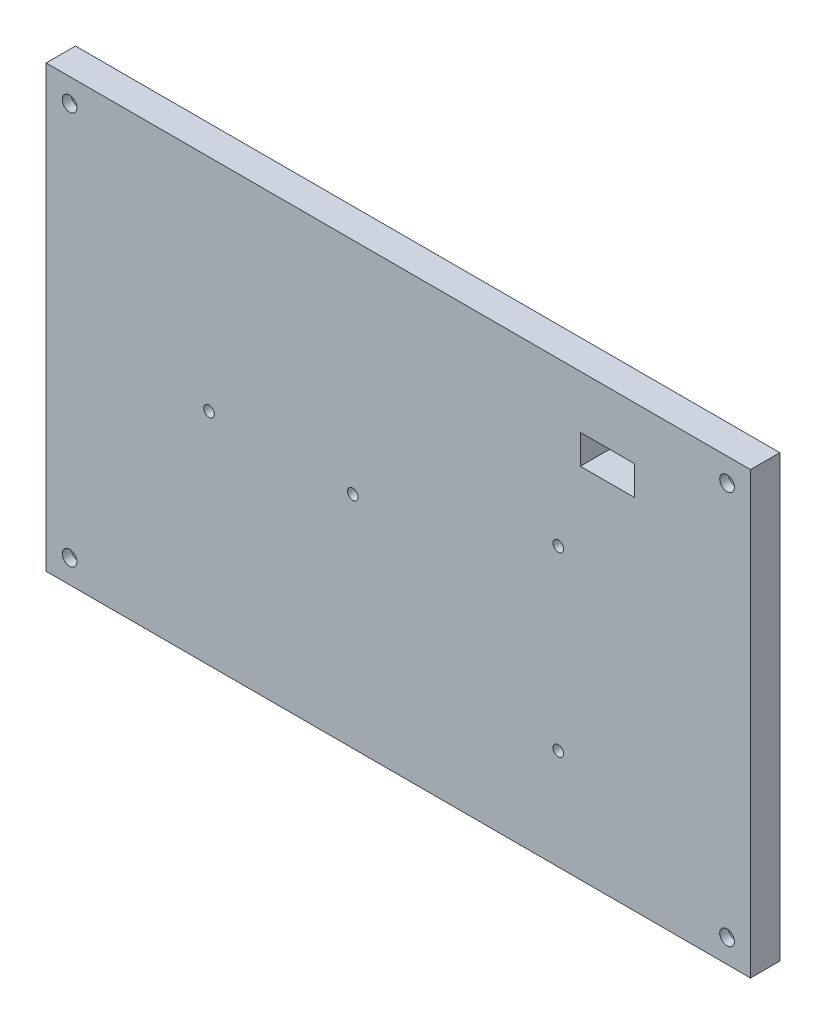
SolidWorks part; units mm, degrees
ref_plane "前视基准面" through (0, 0, 0) normal (0, 0, 1) x (1, 0, 0)
ref_plane "上视基准面" through (0, 0, 0) normal (0, 1, 0) x (1, 0, 0)
ref_plane "右视基准面" through (0, 0, 0) normal (1, 0, 0) x (0, 0, -1)
other "Configuration Table"
sketch "草图1" plane through (0, 0, 0) normal (0, 0, 1) x (1, 0, 0)
  line L9 (-120, 37.5) -> (0, 37.5)
  line L10 (-120, 37.5) -> (-120, -37.5)
  line L16 (-120, -37.5) -> (0, -37.5)
  line L17 (0, 37.5) -> (0, -37.5)
  dimension "D2" = 120
  dimension "D1" = 75
extrude "凸台-拉伸1" add sketch "草图1" along normal blind 5 contours L16 L17 L9 L10
sketch "草图2" plane through (0, 0, 0) normal (0, 0, -1) x (-1, 0, 0)
  line L0 (120, 37.5) -> (0, 37.5) construction
  line L1 (0, 37.5) -> (0, -37.5) construction
  line L2 (120, 37.5) -> (120, -37.5) construction
  line L3 (120, -37.5) -> (0, -37.5) construction
  circle A0 centre (4, 33.5) radius 2
  circle A1 centre (116, 33.5) radius 2
  circle A2 centre (4, -33.5) radius 2
  circle A3 centre (116, -33.5) radius 2
  circle A4 centre (4, 33.5) radius 1.25
  circle A5 centre (4, -33.5) radius 1.25
  circle A6 centre (116, -33.5) radius 1.25
  circle A7 centre (116, 33.5) radius 1.25
  dimension "D1" = 2.5
  dimension "D2" = 4
  dimension "D3" = 4
  dimension "D4" = 4
  dimension "D5" = 4
  dimension "D6" = 4
extrude "切除-拉伸1" cut sketch "草图2" against normal through all contours A5 | A6 | A7 | A4
extrude "切除-拉伸2" cut sketch "草图2<3>" against normal blind 3.5 contours A0 | A1 | A3 | A2
sketch "草图2<3>" plane through (0, 0, 0) normal (0, 0, -1) x (-1, 0, 0) same geometry as "草图2"
sketch "草图3" plane through (0, 0, 0) normal (0, 0, -1) x (-1, 0, 0)
  line L0 (0, 37.5) -> (0, -37.5) construction
  line L1 (19.8, 28.5) -> (29, 28.5)
  line L2 (19.8, 28.5) -> (19.8, 23.5)
  line L3 (19.8, 23.5) -> (29, 23.5)
  line L4 (29, 28.5) -> (29, 23.5)
  line L6 (120, 37.5) -> (0, 37.5) construction
  dimension "D1" = 19.8
  dimension "D2" = 9
  dimension "D3" = 5
  dimension "D4" = 9.2
extrude "切除-拉伸3" cut sketch "草图3" against normal through all
sketch "草图4" plane through (0, 0, 5) normal (0, 0, 1) x (1, 0, 0)
  circle A0 centre (-92.25, 0) radius 0.9
  circle A1 centre (-67.75, 0) radius 0.9
  dimension "D1" = 1.8
extrude "切除-拉伸4" cut sketch "草图4" against normal through all
sketch "草图5" plane through (0, 0, 5) normal (0, 0, 1) x (1, 0, 0)
  circle A0 centre (-32.75, 9.85) radius 0.9
  circle A1 centre (-32.75, -20.35) radius 0.9
  dimension "D1" = 1.8
extrude "切除-拉伸5" cut sketch "草图5" against normal through all
